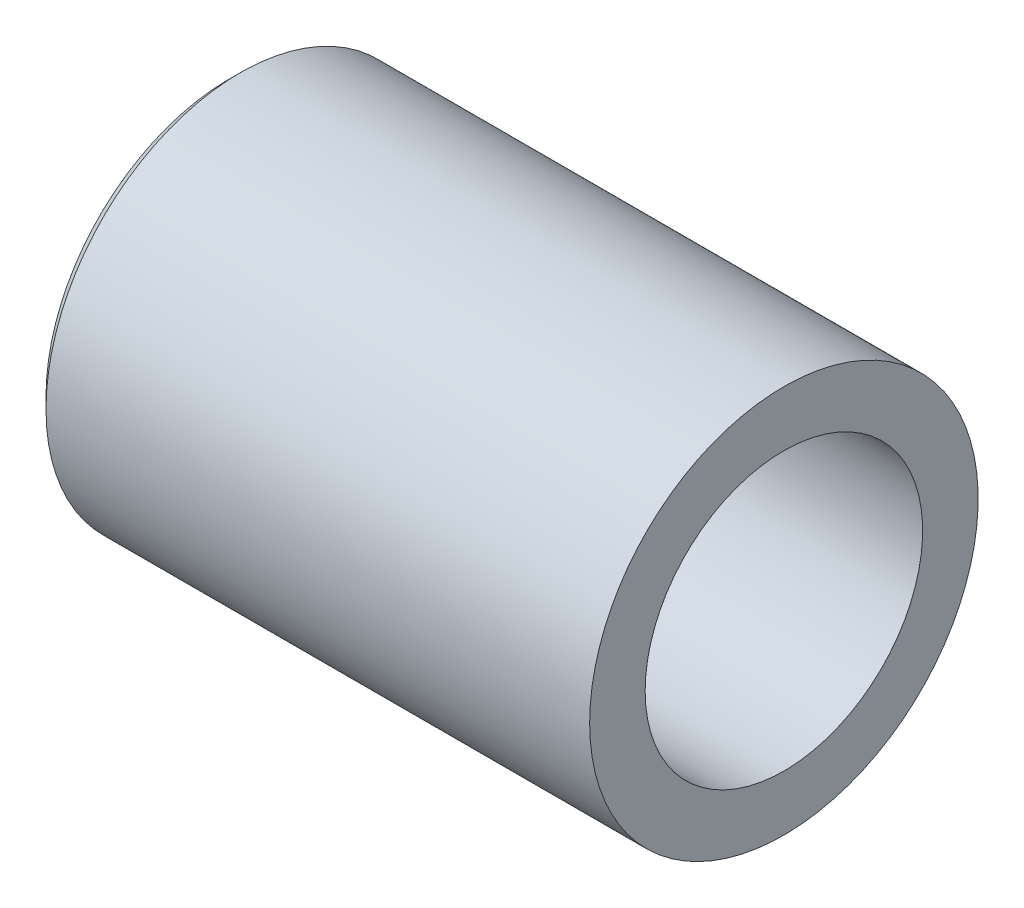
SolidWorks part; units mm, degrees
material "6061-T6 (SS)"
ref_plane "Front Plane" through (0, 0, 0) normal (0, 0, 1) x (1, 0, 0)
ref_plane "Top Plane" through (0, 0, 0) normal (0, 1, 0) x (1, 0, 0)
ref_plane "Right Plane" through (0, 0, 0) normal (1, 0, 0) x (0, 0, -1)
sketch "Sketch1" plane through (0, 0, 0) normal (0, 0, 1) x (1, 0, 0)
  line L0 (0, 0) -> (22.1407, 0) construction
  line L1 (7.4763, 5.5562) -> (23.0266, 5.5563)
  line L3 (7.1588, 3.9688) -> (23.0266, 3.9688)
  line L4 (23.0266, 5.5563) -> (23.0266, 3.9688)
  line L7 (7.1588, -4.1672) -> (7.1588, 4.1672) construction
  line L8 (7.1588, 3.9688) -> (7.1588, 5.2388)
  line L9 (7.1588, 5.2388) -> (7.4763, 5.5562)
  point P7 (7.783, 5.5563)
  dimension "D1" = 7.9375
  dimension "D2" = 1.5875
  dimension "D3" = 1.27
  dimension "D4" = 45
revolve "Revolve1" add sketch "Sketch1" angle 360 about L0
